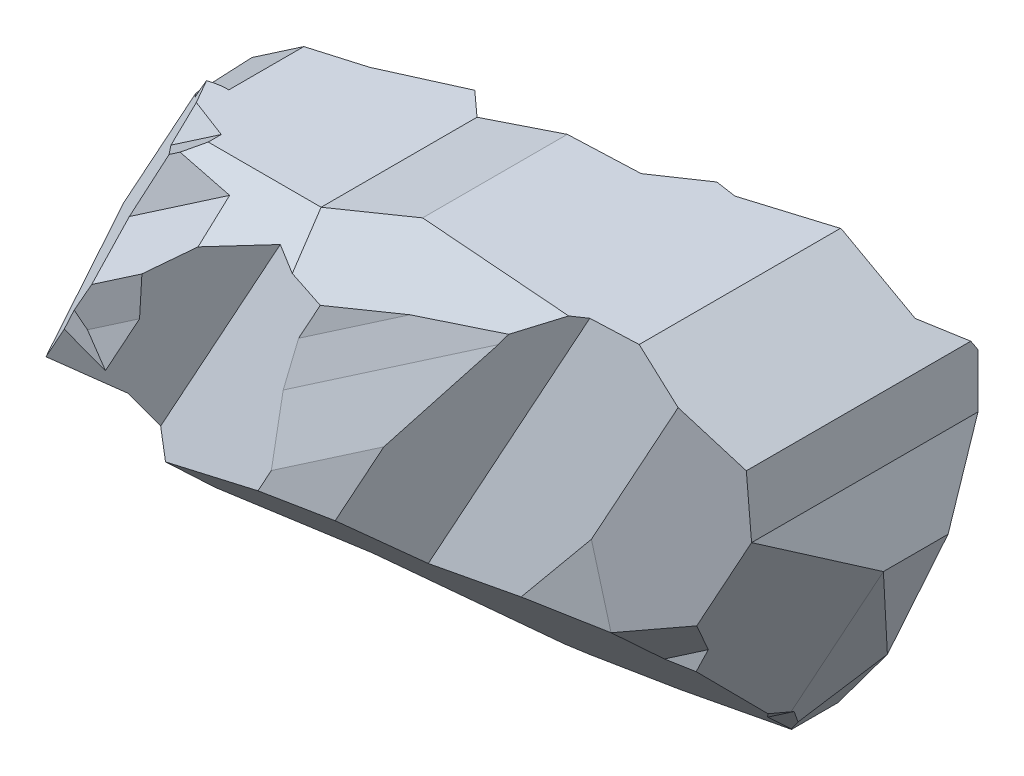
SolidWorks part; units mm, degrees
ref_plane "Front Plane" through (0, 0, 0) normal (0, 0, 1) x (1, 0, 0)
ref_plane "Top Plane" through (0, 0, 0) normal (0, 1, 0) x (1, 0, 0)
ref_plane "Right Plane" through (0, 0, 0) normal (1, 0, 0) x (0, 0, -1)
sketch "Sketch1" plane through (0, 0, 0) normal (0, 0, 1) x (1, 0, 0)
  line L0 (55, 0) -> (-55, 0) construction
  ellipse E0 centre (0, 0) end of major axis (51.6588, 0) minor radius 26.3293 (-36.2676, 18.7496) -> (1.8121, -26.3131) ccw
  spline S0 degree 3 poles (0, 26.3293) (15.0168, 25.039) (45.2457, 18.1207) (16.514, -27.2402) (0, -26.3293) knots 0 0 0 0 0.367873 1 1 1 1
  spline S1 degree 2 poles (0, 26.3293) (-15.7865, 14.5964) (-36.2676, 18.7496) knots 0 0 0 1 1 1
  point P11 (0, 0)
extrude "Boss-Extrude1" add sketch "Sketch1" along normal blind 28.956 contours S0 E0 region at (-8.9581, -0.2666, 0)
sketch "Sketch2" plane through (0, 0, 28.956) normal (0, 0, 1) x (1, 0, 0)
  line L0 (-45.695, 8.9128) -> (-42.6216, 12.7546)
  line L1 (-42.6216, 12.7546) -> (-31.2501, 12.7546)
  line L2 (-31.2501, 12.7546) -> (-23.2593, 12.7546)
  line L3 (-23.2593, 12.7546) -> (-13.1171, 16.9036)
  line L4 (-13.1171, 16.9036) -> (0, 19.055)
  line L5 (0, -15.9258) -> (0, 15.9258) construction
  line L6 (0, 19.055) -> (12.936, 21.1767)
  line L7 (12.936, 21.1767) -> (20.6902, 16.9036)
  line L8 (20.6902, 16.9036) -> (23.4327, 15.3924)
  line L9 (23.4327, 8.9128) -> (26.0724, 2.4602)
  line L10 (26.0724, 2.4602) -> (22.0615, -8.9128)
  line L11 (22.0615, -8.9128) -> (15.2146, -17.4713)
  line L12 (15.2146, -17.4713) -> (2.4732, -21.2058)
  line L13 (2.4732, -21.2058) -> (-6.5585, -22.6872)
  line L14 (-6.5585, -22.6872) -> (-8.7604, -22.6872)
  line L15 (-19.8853, -16.3406) -> (-33.4014, -16.3406)
  line L16 (-33.4014, -16.3406) -> (-38.4725, -8.9128)
  line L17 (-38.4725, -8.9128) -> (-44.1583, -6.9076)
  line L18 (-51.52, -1.9292) -> (-45.695, 8.9128)
  line L19 (23.4327, 15.3924) -> (23.4327, 8.9128)
  line L20 (-19.8853, -16.3406) -> (-8.7604, -22.6872)
  line L21 (-51.52, -1.9292) -> (-44.1583, -6.9076)
  ellipse E0 centre (0, 0) end of major axis (51.6588, 0) minor radius 26.3293 (-36.2676, 18.7496) -> (1.8121, -26.3131) ccw construction
extrude "Cut-Extrude1" cut sketch "Sketch2" against normal blind 28.956 flip side to cut
chamfer "Chamfer1" distance 17.78 angle 45 1 edges at (-2.0427, -21.9465, 28.956)
chamfer "Chamfer2" distance 7.62 angle 45 1 edges at (-18.1882, 14.8291, 28.956)
chamfer "Chamfer3" distance 7.62 angle 45 1 edges at (-22.8779, 12.7546, 28.956)
sketch "Sketch3" plane through (11.9646, 21.712, 0) normal (0.4826, 0.8758, 0) x (0.8758, -0.4826, 0)
  line L0 (-41.8262, -14.7446) -> (-38.4979, -21.336)
  line L1 (-43.4848, -21.336) -> (-26.5268, -21.336) construction
  line L2 (-38.4979, -21.336) -> (-35.0058, -28.2517)
  line L3 (-35.0058, -28.2517) -> (-26.5268, -23.9702)
  line L4 (-26.5268, -23.9702) -> (-15.9677, -28.2517)
  line L5 (-15.9677, -28.2517) -> (-9.8231, -28.2517)
  line L6 (-9.8231, -28.2517) -> (-3.4067, -25.0118)
  line L7 (-3.4067, -25.0118) -> (6.5625, -26.6317)
  line L8 (6.5625, -26.6317) -> (16.2213, -25.0118)
  line L9 (16.2213, 0) -> (16.2213, -28.956) construction
  line L10 (16.2213, -25.0118) -> (21.6474, -14.478)
  line L11 (21.6474, 0) -> (21.6474, -28.956) construction
  line L12 (21.6474, -14.478) -> (23.6236, -10.0683)
  line L13 (23.6236, 0) -> (23.6236, -20.1366) construction
  line L14 (23.6236, -10.0683) -> (16.2213, -2.3845)
  line L15 (16.2213, -2.3845) -> (-1.8296, -2.3845)
  line L16 (-1.8296, -2.3845) -> (-12.8954, -7.9722)
  line L17 (-12.8954, -7.9722) -> (-26.5268, -5.7571)
  line L18 (-26.5268, 0) -> (-26.5268, -21.336) construction
  line L19 (-26.5268, -5.7571) -> (-32.073, 0)
  line L20 (-24.1251, 0) -> (24.1251, 0) construction
  line L21 (-32.073, 0) -> (-38.4364, -6.799)
  line L22 (-38.4364, -6.799) -> (-43.4848, -6.799)
  line L23 (-43.4848, -6.799) -> (-42.3267, -7.8828)
  line L24 (-42.3267, -7.8828) -> (-41.8262, -14.7446)
  line L25 (-43.4848, 0) -> (-43.4848, -21.336) construction
  point P29 (-43.4848, -6.799)
extrude "Cut-Extrude2" cut sketch "Sketch3" against normal blind 60.198 flip side to cut
sketch "Sketch4" plane through (-30.3918, -20.749, 0) normal (-0.8259, -0.5638, 0) x (0, 0, 1)
  line L0 (17.379, 33.9403) -> (20.0338, 30.0113)
  line L1 (20.0338, 30.0113) -> (22.4762, 30.0113)
  line L2 (22.4762, 30.0113) -> (23.1085, 26.3409)
  line L3 (23.1085, 26.3409) -> (27.1485, 23.1089)
  line L4 (27.1485, 23.1089) -> (26.4207, 19.7437)
  line L5 (27.5878, 19.1935) -> (14.7446, 25.2479) construction
  line L6 (26.4207, 19.7437) -> (26.4207, 15.9551)
  line L7 (25.4178, 14.3315) -> (28.2517, 18.9194) construction
  line L8 (26.4207, 15.9551) -> (26.992, 12.6387)
  line L9 (26.992, 12.6387) -> (28.2517, 7.3928)
  line L10 (28.2517, 6.1466) -> (28.2517, 15.1612) construction
  line L11 (28.2517, 7.3928) -> (29.398, 2.6189)
  line L12 (29.398, 2.6189) -> (28.8249, -0.0311)
  line L13 (28.8249, -0.0311) -> (26.6317, -2.7726)
  line L14 (26.6317, -6.8982) -> (26.6317, 5.3288) construction
  line L15 (26.6317, -2.7726) -> (25.8217, -9.96)
  line L16 (25.0118, -13.0217) -> (26.6317, -6.8982) construction
  line L17 (25.8217, -9.96) -> (23.1085, -13.3516)
  line L18 (23.1085, -13.3516) -> (22.5757, -18.0793)
  line L19 (22.5757, -18.0793) -> (14.2571, -21.3848)
  line L20 (14.2571, -21.3848) -> (11.527, -24.7974)
  line L21 (11.527, -24.7974) -> (2.1424, -22.7676)
  line L22 (2.1424, -22.7676) -> (4.3525, -18.0793)
  line L23 (4.3525, -18.0793) -> (2.3845, -14.4182)
  line L24 (2.3845, -13.7974) -> (2.3845, -15.0389) construction
  line L25 (2.3845, -14.4182) -> (2.3845, -11.5018)
  line L26 (2.3845, -9.2061) -> (2.3845, -13.7974) construction
  line L27 (2.3845, -1.4019) -> (5.6011, 2.6189)
  line L28 (5.6011, 2.6189) -> (5.6011, 10.0157)
  line L29 (5.6011, 10.0157) -> (6.5345, 14.3315)
  line L30 (2.7814, 14.3315) -> (25.4178, 14.3315) construction
  line L31 (6.5345, 14.3315) -> (3.9928, 18.0933)
  line L32 (3.9928, 18.0933) -> (1.9998, 23.1089)
  line L33 (1.9998, 23.1089) -> (5.2637, 27.1888)
  line L34 (5.2637, 27.1888) -> (6.799, 29.108)
  line L35 (6.799, 22.0832) -> (6.799, 31.3156) construction
  line L36 (8.2934, 31.9758) -> (15.7862, 31.9758)
  line L37 (6.799, 29.108) -> (8.2934, 31.9758)
  line L38 (2.3845, -1.4019) -> (2.3845, -11.5018)
  arc A0 (15.7862, 31.9758) -> (17.379, 33.9403) centre (17.7941, 31.9758) cw
  point P50 (0, 0)
extrude "Cut-Extrude3" cut sketch "Sketch4" against normal blind 65.532 flip side to cut contours L19 L20 L21 L22 L23 L25 L38 L27 L28 L29 L31 L32 L33 L34 L37 L36 A0 L0 L1 L2 L3 L4 L6 L8 L9 L11 L12 L13 L15 L17 L18
